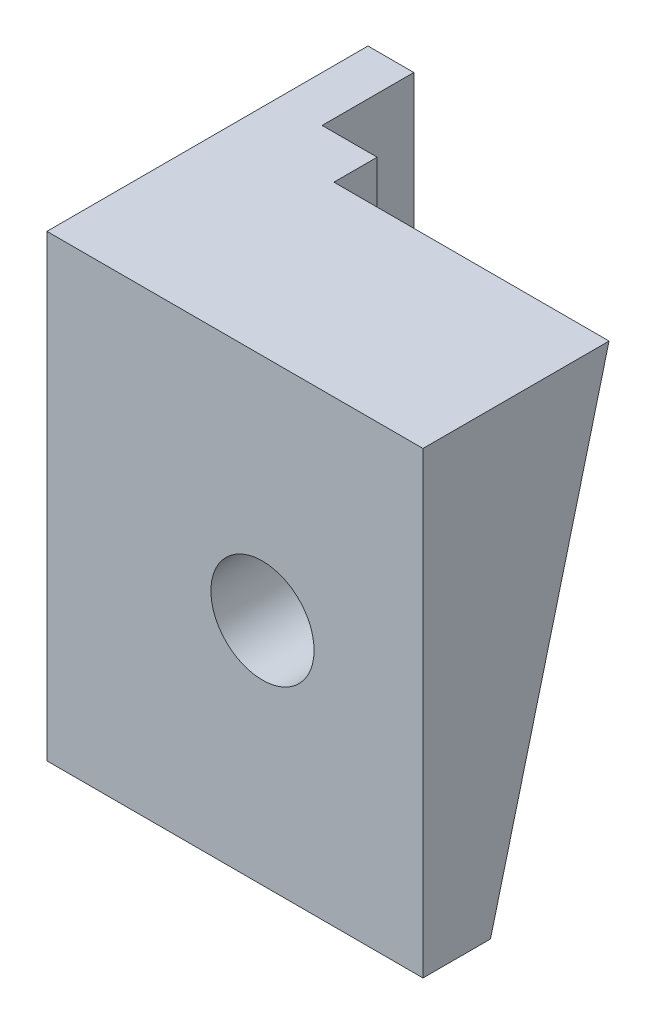
SolidWorks part; units mm, degrees
ref_plane "Front Plane" through (0, 0, 0) normal (0, 0, 1) x (1, 0, 0)
ref_plane "Top Plane" through (0, 0, 0) normal (0, 1, 0) x (1, 0, 0)
ref_plane "Right Plane" through (0, 0, 0) normal (1, 0, 0) x (0, 0, -1)
sketch "Sketch2" plane through (0, 0, 0) normal (0, 0, 1) x (1, 0, 0)
  line L1 (0, 0) -> (1, 0)
  line L2 (0, 0) -> (0, 10)
  line L3 (0, 10) -> (1, 10)
  line L4 (1, 0) -> (1, 10)
  line L5 (1, 0) -> (2.2, 0)
  line L6 (1, 0) -> (1, 10)
  line L7 (1, 10) -> (2.2, 10)
  line L8 (2.2, 0) -> (2.2, 10)
  dimension "D1" = 10
  dimension "D2" = 1
  dimension "D3" = 1.2
extrude "Boss-Extrude1" add sketch "Sketch2" along normal blind 5 contours L5 L8 L7 L4 | L1 L4 L3 L2 region at (0.5, 5, 0) region at (1.6, 5, 0)
extrude "Boss-Extrude2" add sketch "Sketch2<3>" against normal blind 2 contours L1 L4 L3 L2 region at (0.5, 5, 0)
sketch "Sketch2<3>" plane through (0, 0, 0) normal (0, 0, 1) x (1, 0, 0) same geometry as "Sketch2"
sketch "Sketch3" plane through (2.2, 0, 0) normal (1, 0, 0) x (0, 0, -1)
  line L0 (-3.529, 0) -> (-0.9429, 10)
  line L1 (-5, 0) -> (0, 0) construction
  line L2 (-5, 10) -> (0, 10) construction
  line M3 (0, 10) -> (-5, 10)
  line M4 (-5, 10) -> (-5, 0)
  line M5 (-5, 0) -> (0, 0)
  dimension "D1" = 1.471
  dimension "D2" = 75.5
extrude "Boss-Extrude3" add sketch "Sketch3" along normal blind 6 contours L0 M5 M3 M4 region at (2.2, 5.7797, 3.5171)
sketch "Sketch4" plane through (0, 0, 5) normal (0, 0, 1) x (1, 0, 0)
  line L0 (0, 10) -> (8.2, 10) construction
  line L2 (8.2, 10) -> (8.2, 0) construction
  circle A0 centre (4.7, 5) radius 1.125
  dimension "D1" = 2.25
  dimension "D2" = 5
  dimension "D3" = 3.5
extrude "Cut-Extrude1" cut sketch "Sketch4" against normal blind 6
